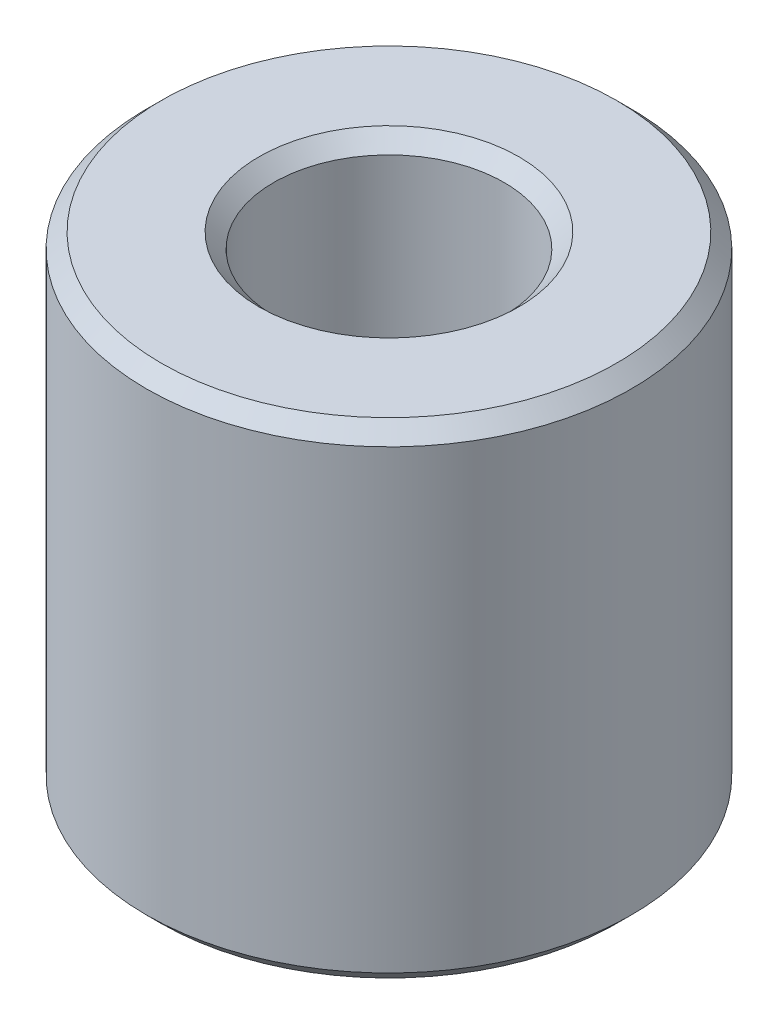
SolidWorks part; units mm, degrees
ref_plane "Front Plane" through (0, 0, 0) normal (0, 0, 1) x (1, 0, 0)
ref_plane "Top Plane" through (0, 0, 0) normal (0, 1, 0) x (1, 0, 0)
ref_plane "Right Plane" through (0, 0, 0) normal (1, 0, 0) x (0, 0, -1)
sketch "Sketch1" plane through (0, 0, 0) normal (0, 1, 0) x (1, 0, 0)
  circle A0 centre (0, 0) radius 50
  dimension "SLEEVE_OD" = 100
extrude "Boss-Extrude1" add sketch "Sketch1" along normal blind 100.0812
sketch "Sketch2" plane through (0, 0, 0) normal (0, 1, 0) x (1, 0, 0)
  circle A0 centre (0, 0) radius 23.7608
  dimension "BORE_D" = 47.5216
extrude "Cut-Extrude1" cut sketch "Sketch2" along normal through all
chamfer "Chamfer1" distance 3.0566 angle 45 4 edges at (0, 100.0812, 23.7608) (0, 0, 23.7608) (0, 0, 50) (0, 100.0812, 50)
